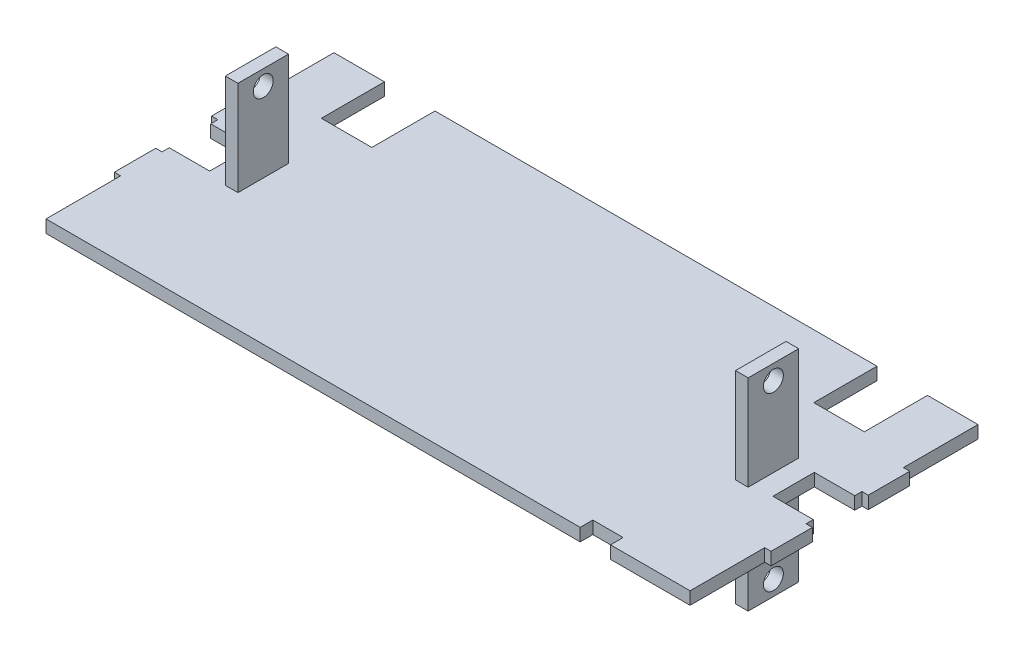
SolidWorks part; units mm, degrees
ref_plane "Front Plane" through (0, 0, 0) normal (0, 0, 1) x (1, 0, 0)
ref_plane "Top Plane" through (0, 0, 0) normal (0, 1, 0) x (1, 0, 0)
ref_plane "Right Plane" through (0, 0, 0) normal (1, 0, 0) x (0, 0, -1)
sketch "Sketch1" plane through (0, 0, 0) normal (0, 1, 0) x (1, 0, 0)
  line L0 (0, 72.39) -> (0, -72.39) construction
  line L1 (161.925, -72.39) -> (121.92, -72.39)
  line L2 (161.925, -72.39) -> (161.925, -34.8747)
  line L3 (161.925, 72.39) -> (136.525, 72.39)
  line L4 (-161.925, -72.39) -> (-161.925, -34.8747)
  line L5 (161.925, -72.39) -> (-161.925, 72.39) construction
  line L6 (161.925, 72.39) -> (-161.925, -72.39) construction
  line L7 (161.925, 10.414) -> (141.605, 10.414)
  line L9 (161.925, -10.414) -> (141.605, -10.414)
  line L10 (141.605, 10.414) -> (141.605, -10.414)
  line L11 (-136.525, 72.39) -> (-161.925, 72.39)
  line L13 (-161.925, -10.414) -> (-141.605, -10.414)
  line L14 (-141.605, 10.414) -> (-141.605, -10.414)
  line L15 (-161.925, 10.414) -> (-141.605, 10.414)
  line L17 (-127, 0) -> (127, 0) construction
  line L18 (-161.925, 14.0467) -> (-165.1, 14.0467)
  line L20 (-161.925, 34.8747) -> (-165.1, 34.8747)
  line L21 (-165.1, 14.0467) -> (-165.1, 34.8747)
  line L22 (-161.925, -34.8747) -> (-165.1, -34.8747)
  line L23 (-165.1, -14.0467) -> (-165.1, -34.8747)
  line L24 (-161.925, -14.0467) -> (-165.1, -14.0467)
  line L27 (161.925, -14.0467) -> (165.1, -14.0467)
  line L28 (165.1, -14.0467) -> (165.1, -34.8747)
  line L29 (161.925, -34.8747) -> (165.1, -34.8747)
  line L30 (161.925, 34.8747) -> (165.1, 34.8747)
  line L31 (165.1, 14.0467) -> (165.1, 34.8747)
  line L32 (161.925, 14.0467) -> (165.1, 14.0467)
  line L34 (-161.925, 34.8747) -> (-161.925, 72.39)
  line L35 (-161.925, -14.0467) -> (-161.925, -10.414)
  line L36 (161.925, 34.8747) -> (161.925, 72.39)
  line L37 (161.925, -14.0467) -> (161.925, -10.414)
  line L38 (-161.925, 10.414) -> (-161.925, 14.0467)
  line L39 (161.925, 10.414) -> (161.925, 14.0467)
  line L40 (-136.525, 72.39) -> (-136.525, 40.64)
  line L41 (-136.525, 40.64) -> (-111.125, 40.64)
  line L42 (-111.125, 72.39) -> (-111.125, 40.64)
  line L44 (111.125, 72.39) -> (111.125, 40.64)
  line L45 (111.125, 40.64) -> (136.525, 40.64)
  line L46 (136.525, 72.39) -> (136.525, 40.64)
  line L47 (111.125, 72.39) -> (-111.125, 72.39)
  line L48 (106.68, -72.39) -> (-161.925, -72.39)
  line L50 (106.68, -72.39) -> (106.68, -66.04)
  line L51 (106.68, -66.04) -> (121.92, -66.04)
  line L52 (121.92, -72.39) -> (121.92, -66.04)
  point P0 (0, 0)
  point P6 (127, 0)
  point P47 (121.92, -69.215)
  dimension "D1" = 323.85
  dimension "D2" = 144.78
  dimension "D3" = 20.828
  dimension "D5" = 3.175
  dimension "D6" = 20.828
  dimension "D4" = 20.32
  dimension "D7" = 31.75
  dimension "D8" = 25.4
  dimension "D9" = 25.4
  dimension "D10" = 31.75
  dimension "D12" = 25.4
  dimension "D11" = 25.4
  dimension "D13" = 15.24
  dimension "D14" = 6.35
  dimension "D15" = 40.005
extrude "Boss-Extrude1" add sketch "Sketch1" along normal mid plane 6.35
sketch "Sketch2" plane through (0, 0, 0) normal (0, 1, 0) x (1, 0, 0)
  line L0 (-141.605, 10.414) -> (-141.605, -10.414) construction
  line L1 (125.095, -12.7) -> (131.445, -12.7)
  line L2 (125.095, -12.7) -> (125.095, 12.7)
  line L3 (125.095, 12.7) -> (131.445, 12.7)
  line L4 (131.445, -12.7) -> (131.445, 12.7)
  line L5 (125.095, -12.7) -> (131.445, 12.7) construction
  line L6 (125.095, 12.7) -> (131.445, -12.7) construction
  line L9 (-125.095, -12.7) -> (-125.095, 12.7)
  line L10 (-125.095, 12.7) -> (-131.445, 12.7)
  line L11 (-131.445, -12.7) -> (-131.445, 12.7)
  line L12 (-125.095, -12.7) -> (-131.445, -12.7)
  line L13 (141.605, -10.414) -> (141.605, 10.414) construction
  point P0 (128.27, 0)
  point P10 (141.605, 0)
  dimension "D1" = 10.16
  dimension "D2" = 10.16
  dimension "D3" = 25.4
  dimension "D4" = 25.4
  dimension "D5" = 6.35
  dimension "D6" = 6.35
  dimension "D7" = 6.35
extrude "Boss-Extrude2" add sketch "Sketch2" along normal mid plane 101.6
sketch "Sketch3" plane through (-131.445, 0, 0) normal (-1, 0, 0) x (0, 0, 1)
  line L0 (-12.7, 50.8) -> (12.7, 50.8) construction
  line L1 (-12.7, -50.8) -> (12.7, -50.8) construction
  circle A0 centre (0, 43.18) radius 5.0038
  circle A1 centre (0, -43.18) radius 5.0038
  point P4 (0, 50.8)
  dimension "D1" = 10.0076
  dimension "D2" = 10.0076
  dimension "D3" = 7.62
  dimension "D4" = 7.62
  dimension "D5" = 86.36
extrude "Cut-Extrude1" cut sketch "Sketch3" against normal through all both and the other way through all
equation "\"length\"= 12.75"
equation "\"width\"= 5.7"
equation "\"height\"= 0.25"
equation "\"D1@Sketch1\"=\"length\""
equation "\"D2@Sketch1\"=\"width\""
equation "\"eyebolt width\"= 0.82"
equation "\"eyebolt length\"= 0.8"
equation "\"D3@Sketch1\"=\"eyebolt width\""
equation "\"D4@Sketch1\"=\"eyebolt length\""
equation "\"lead screw holder height\"= 2.76"
equation "\"lead screw diameter\"=0.394"
equation "\"D1@Sketch3\"=\"lead screw diameter\""
equation "\"distance from holders to board\"=0.4"
equation "\"D2@Sketch3\"=\"lead screw diameter\""
equation "\"lead_screw_dist\"=3.4"
equation "\"D5@Sketch3\"=\"lead_screw_dist\""
